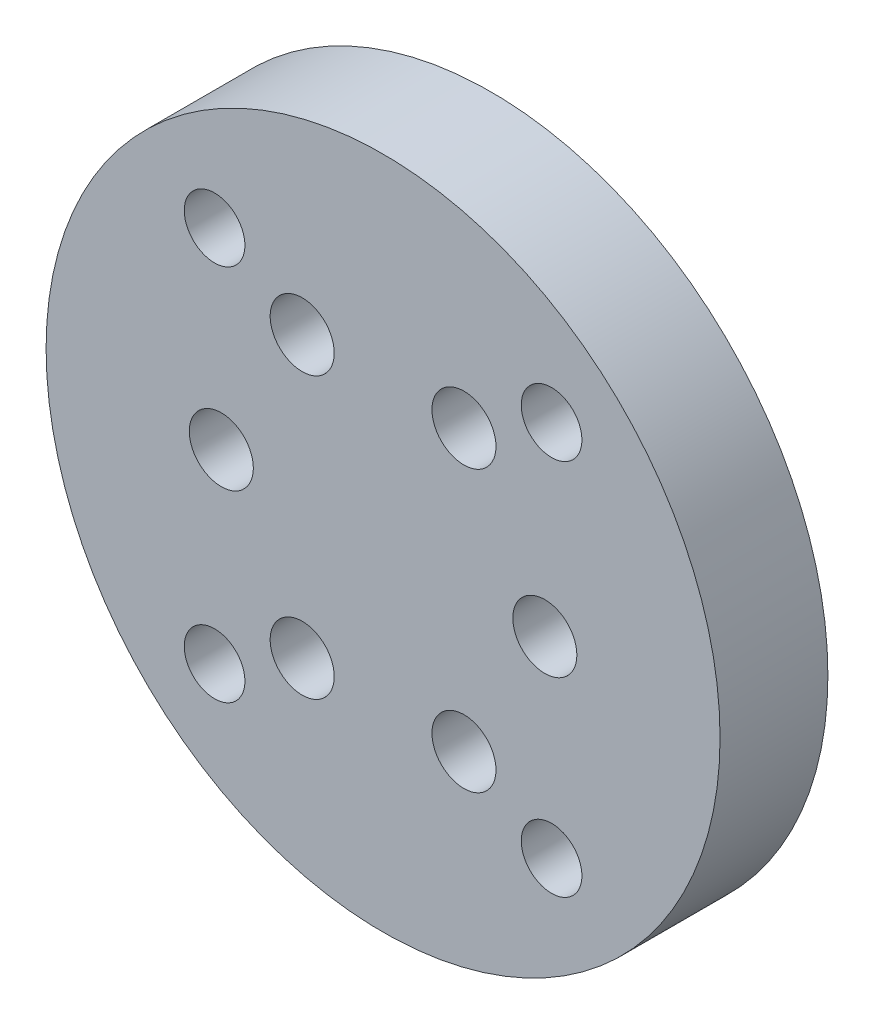
SolidWorks part; units mm, degrees
ref_plane "Front Plane" through (0, 0, 0) normal (0, 0, 1) x (1, 0, 0)
ref_plane "Top Plane" through (0, 0, 0) normal (0, 1, 0) x (1, 0, 0)
ref_plane "Right Plane" through (0, 0, 0) normal (1, 0, 0) x (0, 0, -1)
sketch "Sketch2" plane through (0, 0, 0) normal (0, 0, 1) x (1, 0, 0)
  circle A0 centre (-15.028, -11.4071) radius 4.025
  circle A1 centre (-9.028, -1.0148) radius 4.025
  circle A2 centre (2.972, -1.0148) radius 4.025
  circle A3 centre (8.972, -11.4071) radius 4.025
  circle A4 centre (2.972, -21.7994) radius 4.025
  circle A5 centre (-9.028, -21.7994) radius 4.025
  circle A28 centre (8.972, -11.4071) radius 1.625 construction
  circle A30 centre (2.972, -1.0148) radius 1.625 construction
  circle A31 centre (-3.028, -11.4071) radius 6.25 construction
  circle A32 centre (2.972, -21.7994) radius 1.625 construction
  circle A34 centre (-9.028, -21.7994) radius 1.625 construction
  circle A35 centre (-15.028, -11.4071) radius 1.625 construction
  circle A37 centre (-9.028, -1.0148) radius 1.625 construction
  circle A38 centre (-9.028, -1.0148) radius 1.625
  circle A40 centre (-15.028, -11.4071) radius 1.625
  circle A41 centre (-9.028, -21.7994) radius 1.625
  circle A43 centre (2.972, -21.7994) radius 1.625
  circle A44 centre (-3.028, -11.4071) radius 6.25
  circle A45 centre (2.972, -1.0148) radius 1.625
  circle A47 centre (8.972, -11.4071) radius 1.625
  circle A52 centre (-3.028, -11.4071) radius 25
  circle A53 centre (-15.028, -11.4071) radius 2.375
  circle A54 centre (-9.028, -1.0148) radius 2.375
  circle A55 centre (-9.028, -21.7994) radius 2.375
  circle A56 centre (2.972, -21.7994) radius 2.375
  circle A57 centre (8.972, -11.4071) radius 2.375
  circle A58 centre (2.972, -1.0148) radius 2.375
  point P36 (-3.028, -11.4071)
  dimension "D1" = 0.75
  dimension "D2" = 50
  dimension "D3" = 1.65
extrude "Boss-Extrude2" add sketch "Sketch2" along normal blind 8 contours A52 A0 A1 A2 A3 A4 A5 A44 | A0 A53 | A44 | A1 A54 | A2 A58 | A3 A57 | A4 A56 | A5 A55 region at (-18.9392, -11.4071, 0) region at (-12.9392, -1.0148, 0) region at (-0.9392, -1.0148, 0) region at (5.0608, -11.4071, 0) region at (-0.9392, -21.7994, 0) region at (-12.9392, -21.7994, 0) region at (-3.028, -11.4071, 0) region at (-27.3209, -11.4071, 0)
sketch "Sketch3" plane through (0, 0, 0) normal (0, 0, -1) x (-1, 0, 0)
  line L1 (-9.472, -25.4071) -> (15.528, -25.4071) construction
  line L2 (-9.472, -25.4071) -> (-9.472, 2.5929) construction
  line L3 (-9.472, 2.5929) -> (15.528, 2.5929) construction
  line L4 (15.528, -25.4071) -> (15.528, 2.5929) construction
  line L5 (-9.472, -25.4071) -> (15.528, 2.5929) construction
  line L6 (-9.472, 2.5929) -> (15.528, -25.4071) construction
  circle A8 centre (-9.472, 2.5929) radius 2.25
  circle A9 centre (15.528, 2.5929) radius 2.25
  circle A10 centre (15.528, -25.4071) radius 2.25
  circle A11 centre (-9.472, -25.4071) radius 2.25
  point P0 (3.028, -11.4071)
  point P9 (0, 0)
  point P10 (0, 0)
  point P11 (0, 0)
  point P12 (0, 0)
  point P13 (0, 0)
  point P14 (0, 0)
  point P15 (0, 0)
  point P16 (0, 0)
  dimension "D1" = 4.5
  dimension "D2" = 25
  dimension "D3" = 28
extrude "Cut-Extrude1" cut sketch "Sketch3" against normal through all both and the other way through all contours A8 | A9 | A10 | A11
extrude "Cut-Extrude2" cut sketch "Sketch2<4>" along normal blind 4 from surface contours A2 A58 | A3 A57 | A4 A56 | A5 A55 | A1 A54 | A0 A53 region at (-18.9392, -11.4071, 0) region at (-12.9392, -1.0148, 0) region at (-0.9392, -1.0148, 0) region at (5.0608, -11.4071, 0) region at (-0.9392, -21.7994, 0) region at (-12.9392, -21.7994, 0) starting at face at (21.972, -11.4071, 0)
sketch "Sketch2<4>" plane through (0, 0, 0) normal (0, 0, 1) x (1, 0, 0) same geometry as "Sketch2"
